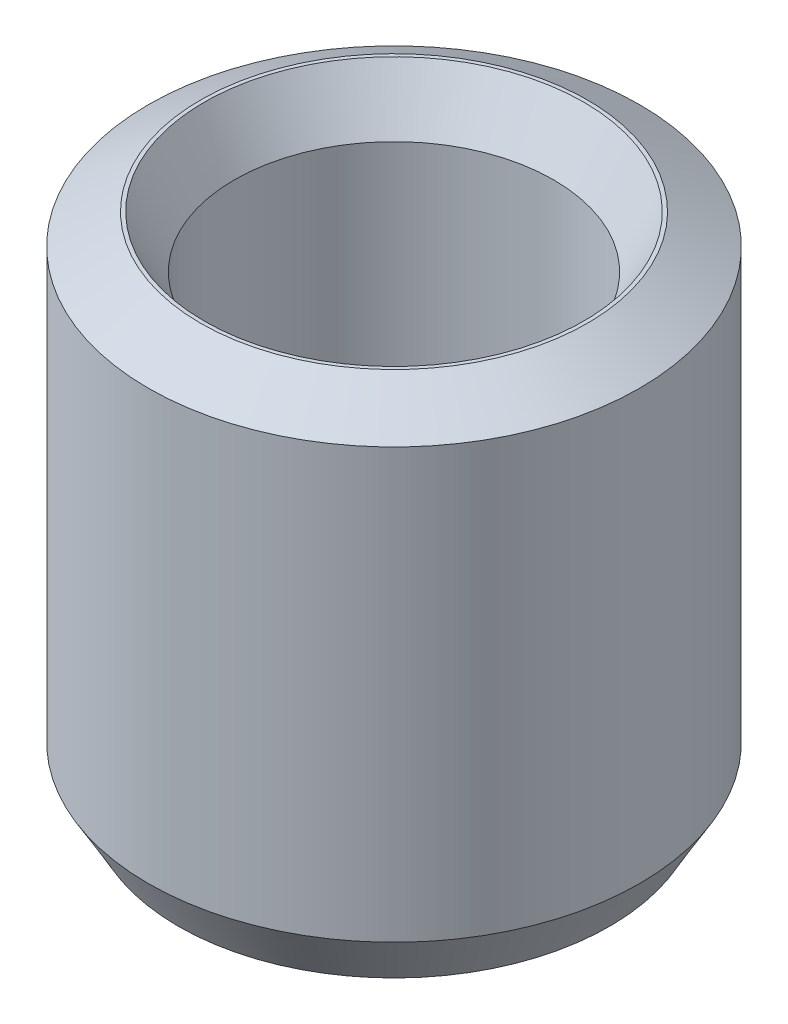
SolidWorks part; units mm, degrees
ref_plane "Front Plane" through (0, 0, 0) normal (0, 0, 1) x (1, 0, 0)
ref_plane "Top Plane" through (0, 0, 0) normal (0, 1, 0) x (1, 0, 0)
ref_plane "Right Plane" through (0, 0, 0) normal (1, 0, 0) x (0, 0, -1)
sketch "Sketch1" plane through (0, 0, 0) normal (0, 1, 0) x (1, 0, 0)
  circle A0 centre (0, 0) radius 7.5
  dimension "SLEEVE_OD" = 15
extrude "Boss-Extrude1" add sketch "Sketch1" along normal blind 15.6125
sketch "Sketch2" plane through (0, 0, 0) normal (0, 1, 0) x (1, 0, 0)
  circle A0 centre (0, 0) radius 4.8722
  dimension "BORE_D" = 9.7444
extrude "Cut-Extrude1" cut sketch "Sketch2" along normal through all
chamfer "Chamfer1" distance 0.9205 angle 60 4 edges at (0, 15.6125, 4.8722) (0, 0, 4.8722) (0, 0, 7.5) (0, 15.6125, 7.5) first distance on face at (0, 15.6125, 4.8722) first distance on face at (0, 0, 4.8722) first distance on face at (0, 15.6125, 7.5)
